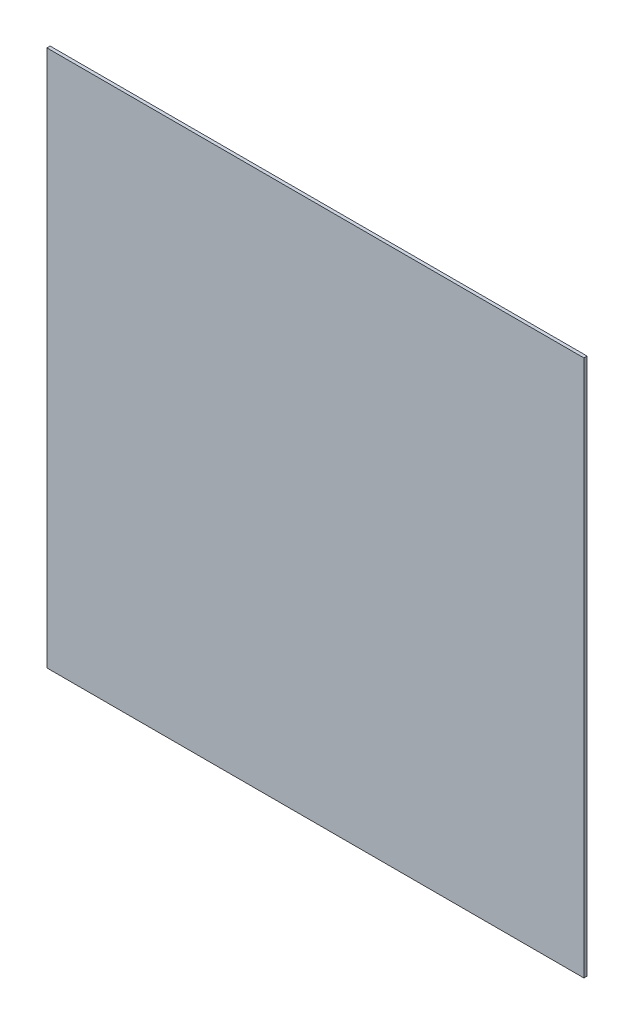
SolidWorks part; units mm, degrees
material "AISI 316 Annealed Stainless Steel Bar (SS)"
ref_plane "Front Plane" through (0, 0, 0) normal (0, 0, 1) x (1, 0, 0)
ref_plane "Top Plane" through (0, 0, 0) normal (0, 1, 0) x (1, 0, 0)
ref_plane "Right Plane" through (0, 0, 0) normal (1, 0, 0) x (0, 0, -1)
sketch "Sketch1" plane through (0, 0, 0) normal (0, 0, 1) x (1, 0, 0)
  line L1 (250, -250) -> (-250, -250)
  line L2 (250, -250) -> (250, 250)
  line L3 (250, 250) -> (-250, 250)
  line L4 (-250, -250) -> (-250, 250)
  line L5 (250, -250) -> (-250, 250) construction
  line L6 (250, 250) -> (-250, -250) construction
  point P0 (0, 0)
  dimension "D1" = 500
  dimension "D2" = 500
extrude "Boss-Extrude1" add sketch "Sketch1" along normal mid plane 3
